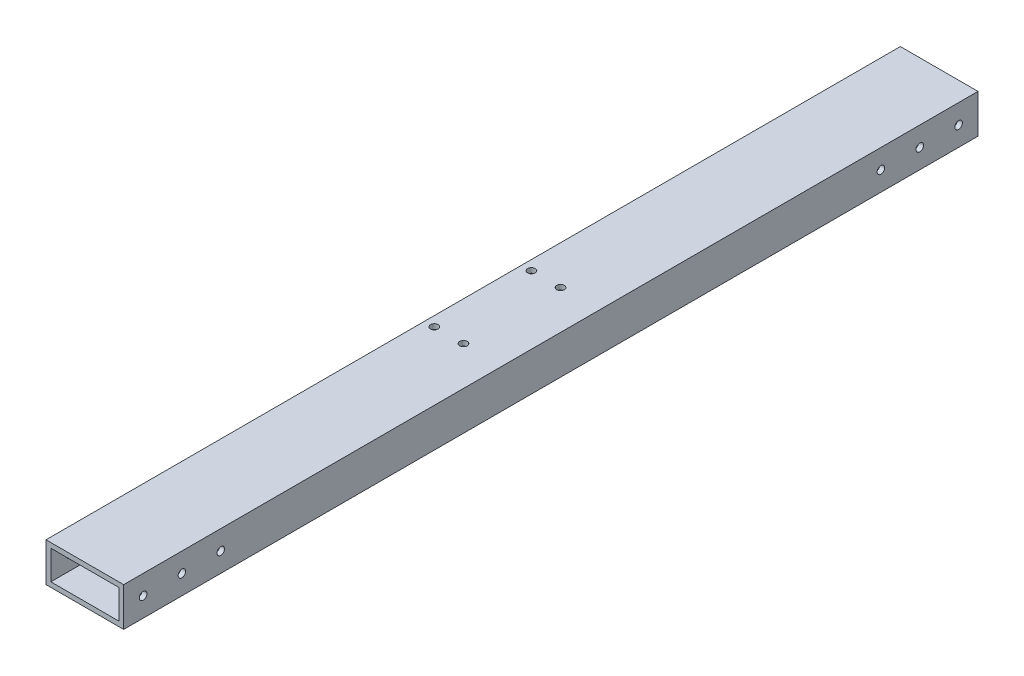
SolidWorks part; units mm, degrees
material "6061-T6 (SS)"
ref_plane "Front Plane" through (0, 0, 0) normal (0, 0, 1) x (1, 0, 0)
ref_plane "Top Plane" through (0, 0, 0) normal (0, 1, 0) x (1, 0, 0)
ref_plane "Right Plane" through (0, 0, 0) normal (1, 0, 0) x (0, 0, -1)
sketch "Sketch1" plane through (0, 0, 0) normal (0, 0, 1) x (1, 0, 0)
  line L1 (-25.4, -12.7) -> (25.4, -12.7)
  line L2 (-25.4, -12.7) -> (-25.4, 12.7)
  line L3 (-25.4, 12.7) -> (25.4, 12.7)
  line L4 (25.4, -12.7) -> (25.4, 12.7)
  line L5 (-25.4, -12.7) -> (25.4, 12.7) construction
  line L6 (-25.4, 12.7) -> (25.4, -12.7) construction
  point P0 (0, 0)
  dimension "D1" = 50.8
  dimension "D2" = 25.4
extrude "Boss-Extrude1" add sketch "Sketch1" along normal mid plane 558.8
shell "Shell1" thickness 3.175 removed face at (0, 0, -279.4) removed face at (0, 0, 279.4)
sketch "Sketch3" plane through (0, 0, 0) normal (1, 0, 0) x (0, 0, -1)
  line L0 (-279.4, -12.7) -> (-279.4, 12.7) construction
  line L1 (0, 12.7) -> (0, -12.7) construction
  line L2 (-279.4, 12.7) -> (279.4, 12.7) construction
  line L3 (-279.4, -12.7) -> (279.4, -12.7) construction
  circle A0 centre (-266.7, 0) radius 2.4892
  circle A1 centre (-241.3, 0) radius 2.4892
  circle A2 centre (-215.9, 0) radius 2.4892
  circle A3 centre (215.9, 0) radius 2.4892
  circle A4 centre (241.3, 0) radius 2.4892
  circle A5 centre (266.7, 0) radius 2.4892
  dimension "D2" = 4.9784
  dimension "D1" = 12.7
  dimension "D3" = 25.4
  dimension "D4" = 25.4
  dimension "D5" = 12.7
extrude "Cut-Extrude1" cut sketch "Sketch3" against normal through all both and the other way through all
sketch "Sketch4" plane through (0, 0, 0) normal (0, 1, 0) x (1, 0, 0)
  line L1 (-25.4, -279.4) -> (-25.4, 279.4) construction
  circle A0 centre (0, -31.75) radius 2.4892
  circle A1 centre (-19.05, -31.75) radius 2.4892
  circle A2 centre (0, 31.75) radius 2.4892
  circle A3 centre (-19.05, 31.75) radius 2.4892
  dimension "D1" = 4.9784
  dimension "D3" = 19.05
  dimension "D4" = 31.75
  dimension "D2" = 6.35
  dimension "D5" = 63.5
extrude "Cut-Extrude2" cut sketch "Sketch4" against normal through all both and the other way through all
equation "\"D4@Sketch3\"=\"D3@Sketch3\""
equation "\"D4@Sketch4\"=1.5-.25"
